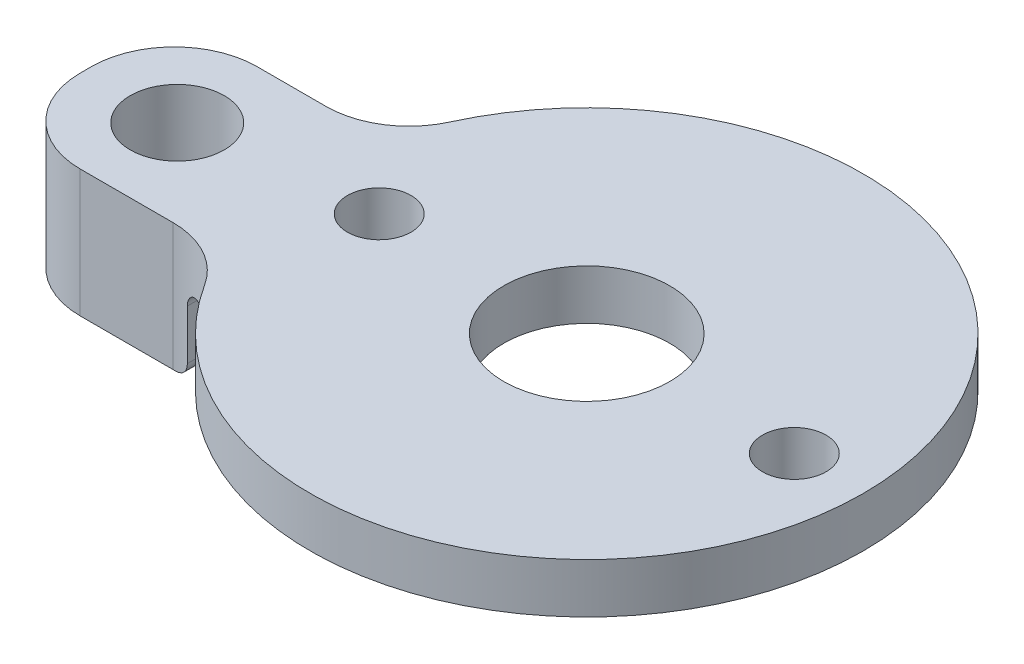
SolidWorks part; units mm, degrees
ref_plane "Front Plane" through (0, 0, 0) normal (0, 0, 1) x (1, 0, 0)
ref_plane "Top Plane" through (0, 0, 0) normal (0, 1, 0) x (1, 0, 0)
ref_plane "Right Plane" through (0, 0, 0) normal (1, 0, 0) x (0, 0, -1)
sketch "Sketch1" plane through (0, 0, 0) normal (0, 1, 0) x (1, 0, 0)
  line L0 (-12.3288, 3.048) -> (-21.9808, 3.048)
  line L1 (-21.9808, 3.048) -> (-21.9808, -5.08)
  line L2 (-21.9808, -5.08) -> (-11.6397, -5.08)
  circle A0 centre (0, 0) radius 3.81
  arc A1 (-11.6397, -5.08) -> (-12.3288, 3.048) centre (0, 0) ccw
  circle A2 centre (9.525, 0) radius 1.4605
  circle A3 centre (-9.525, 0) radius 1.4605
  circle A5 centre (-17.78, -1.016) radius 2.159
  circle A6 centre (-17.78, -1.016) radius 2 construction
  point P13 (-21.9808, -1.016)
  point P17 (-19.05, -1.016)
  dimension "D1" = 7.62
  dimension "D2" = 25.4
  dimension "D3" = 2.921
  dimension "D4" = 2.921
  dimension "D9" = 4.318
  dimension "D5" = 19.05
  dimension "D6" = 9.525
  dimension "D7" = 9.652
  dimension "D8" = 8.128
extrude "Boss-Extrude1" add sketch "Sketch1" along normal blind 2.286
sketch "Sketch3" plane through (0, 0, 0) normal (0, -1, 0) x (1, 0, 0)
  line L0 (-12.3288, -3.048) -> (-21.9808, -3.048) construction
  line L1 (-21.9808, 5.08) -> (-13.1824, 5.08)
  line L2 (-21.9808, 5.08) -> (-21.9808, -3.048)
  line L3 (-21.9808, -3.048) -> (-13.1824, -3.048)
  line L4 (-13.1824, 5.08) -> (-13.1824, -3.048)
  circle A1 centre (-17.78, 1.016) radius 2.159
extrude "Boss-Extrude2" add sketch "Sketch3" along normal blind 3.556
fillet "Fillet1" radius 3.81 2 edges at (-21.9808, -0.635, 5.08) (-21.9808, -0.635, -3.048)
fillet "Fillet2" radius 3.81 2 edges at (-12.3288, 1.143, -3.048) (-11.6397, 1.143, 5.08)
fillet "Fillet3" radius 0.635 2 edges at (-13.1824, 0, 0.8155) (-13.1824, -3.556, 0.8155)
